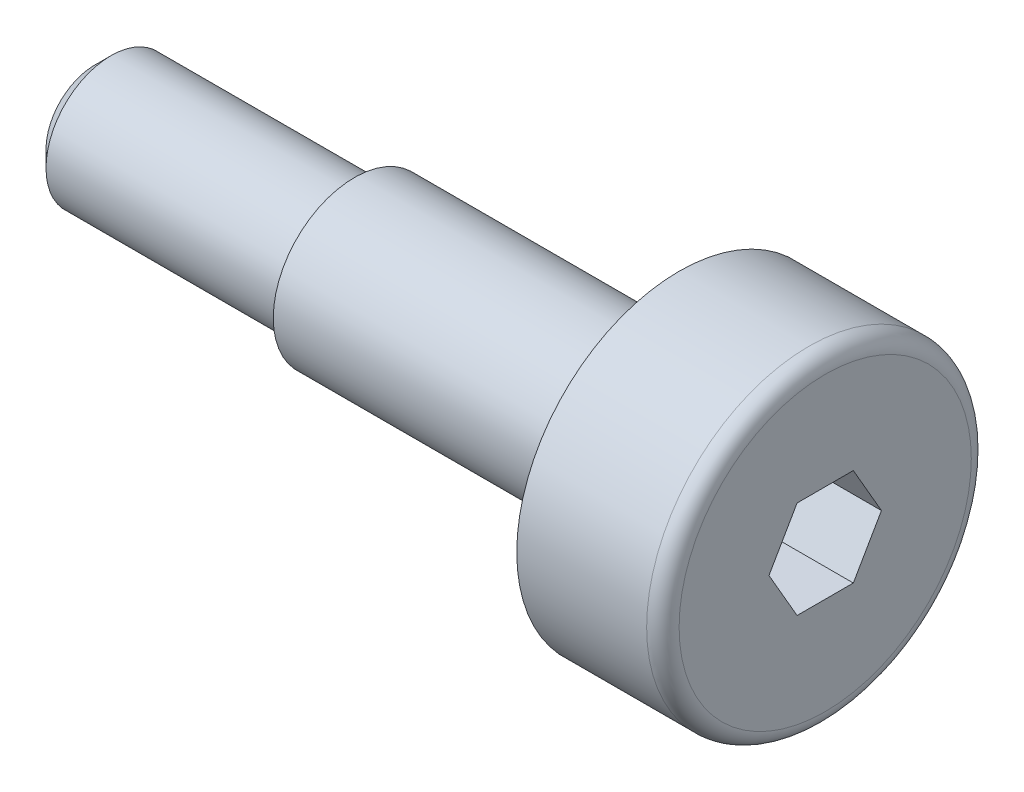
SolidWorks part; units mm, degrees
material "AISI 1020"
ref_plane "XY (Front)" through (0, 0, 0) normal (0, 0, 1) x (1, 0, 0)
ref_plane "XZ (Top)" through (0, 0, 0) normal (0, 1, 0) x (1, 0, 0)
ref_plane "YZ (Right)" through (0, 0, 0) normal (1, 0, 0) x (0, 0, -1)
ref_axis "X" through (-25.2, 0, 0) along (1, 0, 0)
ref_axis "Y" through (0, 5.5, 0) along (0, -1, 0)
ref_axis "Z" through (0, 0, -5.5) along (0, 0, 1)
sketch "Sketch1" plane through (0, 0, 0) normal (0, 0, 1) x (1, 0, 0)
  line L0 (0, 0) -> (0, 4.5)
  line L1 (-0.5, 5) -> (-4.5, 5)
  line L2 (-4.5, 5) -> (-4.5, 2.5)
  line L3 (-4.5, 2.5) -> (-14.5, 2.5)
  line L4 (-14.5, 2.5) -> (-14.5, 2)
  line L5 (-14.5, 2) -> (-22.5, 2)
  line L6 (-22.5, 2) -> (-22.5, 0)
  line L7 (-22.5, 0) -> (0, 0)
  line L8 (0, 0) -> (5.7531, 0) construction
  arc A0 (0, 4.5) -> (-0.5, 5) centre (-0.5, 4.5) ccw
  dimension "R" = 0.5
  dimension "d3" = 10
  dimension "d1" = 5
  dimension "M" = 4
  dimension "l3" = 4.5
  dimension "l1" = 10
  dimension "l2" = 8
revolve "Revolve1" add sketch "Sketch1" angle 360 about L8
chamfer "Chamfer1" distance 0.5 angle 45 1 edges at (-22.5, 0, 2)
sketch "Sketch2" plane through (0, 0, 0) normal (1, 0, 0) x (0, 0, -1)
  line L1 (1.7321, 0) -> (0.866, 1.5)
  line L2 (0.866, 1.5) -> (-0.866, 1.5)
  line L3 (-0.866, 1.5) -> (-1.7321, 0)
  line L4 (-1.7321, 0) -> (-0.866, -1.5)
  line L5 (-0.866, -1.5) -> (0.866, -1.5)
  line L6 (0.866, -1.5) -> (1.7321, 0)
  circle A0 centre (0, 0) radius 1.5 construction
  dimension "AF" = 3
extrude "Cut-Extrude1" cut sketch "Sketch2" against normal blind 2.4
